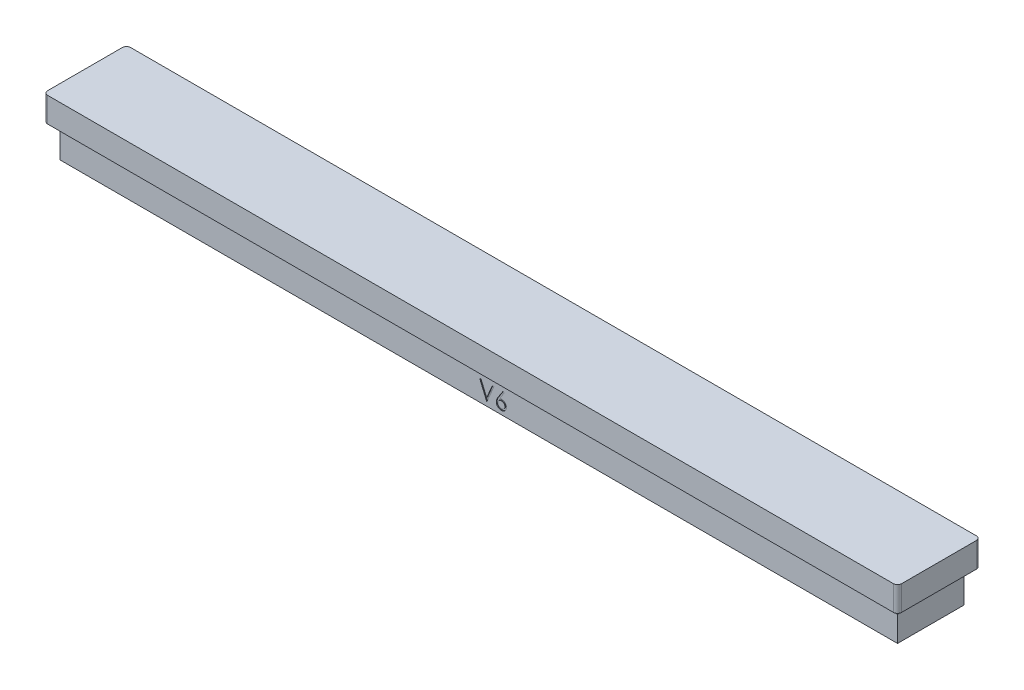
SolidWorks part; units mm, degrees
ref_plane "Front Plane" through (0, 0, 0) normal (0, 0, 1) x (1, 0, 0)
ref_plane "Top Plane" through (0, 0, 0) normal (0, 1, 0) x (1, 0, 0)
ref_plane "Right Plane" through (0, 0, 0) normal (1, 0, 0) x (0, 0, -1)
sketch "Sketch1" plane through (0, 0, 0) normal (0, 1, 0) x (1, 0, 0)
  line L0 (-50.5, 4) -> (-50.5, -4)
  line L1 (-49.5, 3) -> (49.5, 3)
  line L2 (-49.5, 3) -> (-49.5, -3)
  line L3 (-49.5, -3) -> (49.5, -3)
  line L4 (49.5, 3) -> (49.5, -3)
  line L5 (-49.5, 3) -> (49.5, -3) construction
  line L6 (-49.5, -3) -> (49.5, 3) construction
  line L7 (-50.5, -4) -> (50.5, -4)
  line L8 (50.5, 4) -> (50.5, -4)
  line L9 (-50.5, 4) -> (50.5, 4)
  point P0 (0, 0)
  dimension "D1" = 6
  dimension "D2" = 99
  dimension "D3" = 1
extrude "Boss-Extrude1" add sketch "Sketch1" along normal blind 10
sketch "Sketch2" plane through (0, 0, 0) normal (0, -1, 0) x (1, 0, 0)
  line L0 (0, 0) -> (74.3491, 0) construction
  line L1 (48, 0) -> (48, 10.5) construction
  line L2 (50.5, 4) -> (50.5, -4) construction
  line L4 (50.5, 4) -> (67.4224, 4) construction
  line L5 (50.5, -4) -> (69.4178, -4) construction
  line L7 (48, 4) -> (50.5, 4)
  line L9 (48, -4) -> (50.5, -4)
  line L11 (48, 0) -> (48, -8.5) construction
  line L15 (50.5, 4) -> (50.5, 13)
  line L16 (50.5, 13) -> (50, 13) construction
  line L17 (50.5, -4) -> (50.5, -11)
  line L18 (50.5, -11) -> (50, -11) construction
  line L19 (48, 10.5) -> (48, 4)
  line L20 (48, -8.5) -> (48, -4)
  line L21 (-50.5, 4) -> (-50.5, 13) construction
  line L22 (-50.5, 13) -> (-64.4, 13) construction
  line L23 (-66.4, 15) -> (-48.8351, 15)
  line L24 (-48.8351, 15) -> (-48.8351, 4)
  line L25 (-50.5, 4) -> (50.5, 4) construction
  line L26 (-66.4, 11) -> (-51.9017, 11)
  line L27 (-50.5, -4) -> (-59.3527, -4) construction
  line L28 (-51.9017, 11) -> (-51.9017, -4)
  line L29 (-51.9017, -4) -> (-50.5, -4)
  line L30 (-50.5, -4) -> (-50.5, 4)
  line L31 (-50.5, 4) -> (-48.8351, 4)
  line L32 (-64.4, 13) -> (-65.2, 13) construction
  line L33 (-65.2, 13) -> (-66.4, 13) construction
  line L34 (48, 10.5) -> (48, 11) construction
  line L35 (48, 11) -> (48, 13) construction
  line L36 (48, 11) -> (48, 10.5) construction
  line L37 (48, -8.5) -> (48, -9) construction
  line L38 (48, -9) -> (48, -11) construction
  line L39 (48, -9) -> (48, -8.5) construction
  circle A0 centre (48, 13) radius 1.2
  circle A4 centre (48, -11) radius 1.2
  arc A5 (50.5, -11) -> (48, -8.5) centre (48, -11) ccw construction
  arc A8 (48, 10.5) -> (50.5, 13) centre (48, 13) ccw construction
  circle A10 centre (-66.4, 13) radius 1.2
  arc A11 (-66.4, 15) -> (-66.4, 11) centre (-66.4, 13) ccw
  arc A12 (-64.4, 13) -> (-66.4, 15) centre (-66.4, 13) ccw construction
  arc A13 (-66.4, 11) -> (-64.4, 13) centre (-66.4, 13) ccw construction
  arc A14 (50.5, 13) -> (48, 10.5) centre (48, 13) ccw
  arc A15 (48, -8.5) -> (50.5, -11) centre (48, -11) ccw
  dimension "D3" = 2.4
  dimension "D9" = 2.4
  dimension "D10" = 4
  dimension "D1" = 2.5
  dimension "D2" = 13
  dimension "D5" = 11
  dimension "D7" = 9
  dimension "D8" = 15.9
extrude "Boss-Extrude2" [suppressed] add sketch "Sketch2" against normal blind 2
sketch "Sketch3" plane through (0, 10, 0) normal (0, 1, 0) x (1, 0, 0)
  line L0 (51.5, 5) -> (-51.5, 5)
  line L1 (-51.5, 5) -> (-51.5, -5)
  line L2 (-51.5, -5) -> (51.5, -5)
  line L3 (51.5, -5) -> (51.5, 5)
  line L4 (50.5, 4) -> (-50.5, 4)
  line L5 (-50.5, 4) -> (-50.5, -4)
  line L6 (-50.5, -4) -> (50.5, -4)
  line L7 (50.5, -4) -> (50.5, 4)
  line L8 (50.5, 4) -> (-50.5, 4)
  line L9 (-50.5, 4) -> (-50.5, -4)
  line L10 (-50.5, -4) -> (50.5, -4)
  line L11 (50.5, -4) -> (50.5, 4)
  dimension "D1" = 0
  dimension "D2" = 1
extrude "Boss-Extrude3" add sketch "Sketch3" against normal blind 6
fillet "Fillet4" radius 1 1 edges at (0, 4, -4)
fillet "Fillet5" radius 1 1 edges at (0, 4, 4)
fillet "Fillet6" radius 1 1 edges at (50.5, 4, 0)
fillet "Fillet7" radius 1 1 edges at (-50.5, 4, 0)
fillet "Fillet8" [suppressed] radius 0.5
fillet "Fillet9" radius 0.5 4 edges at (51.5, 7, -5) (51.5, 7, 5) (-51.5, 7, 5) (-51.5, 7, -5)
sketch "Sketch4" plane through (0, 10, 0) normal (0, 1, 0) x (1, 0, 0)
  line L4 (51.5, -4.5) -> (51.5, 4.5)
  line L5 (51, 5) -> (-51, 5)
  line L6 (-51.5, 4.5) -> (-51.5, -4.5)
  line L7 (-51, -5) -> (51, -5)
  line L8 (51.5, -4.5) -> (51.5, 4.5)
  line L9 (51, 5) -> (-51, 5)
  line L10 (-51.5, 4.5) -> (-51.5, -4.5)
  line L11 (-51, -5) -> (51, -5)
  arc A4 (51.5, 4.5) -> (51, 5) centre (51, 4.5) ccw
  arc A5 (-51, 5) -> (-51.5, 4.5) centre (-51, 4.5) ccw
  arc A6 (-51.5, -4.5) -> (-51, -5) centre (-51, -4.5) ccw
  arc A7 (51, -5) -> (51.5, -4.5) centre (51, -4.5) ccw
  arc A8 (51.5, 4.5) -> (51, 5) centre (51, 4.5) ccw
  arc A9 (-51, 5) -> (-51.5, 4.5) centre (-51, 4.5) ccw
  arc A10 (-51.5, -4.5) -> (-51, -5) centre (-51, -4.5) ccw
  arc A11 (51, -5) -> (51.5, -4.5) centre (51, -4.5) ccw
  dimension "D1" = 0
extrude "Cut-Extrude1" cut sketch "Sketch4" against normal blind 4
sketch "Sketch5" plane through (0, 0, 4) normal (0, 0, 1) x (1, 0, 0)
  text T0 "V6\r\n\r\n" font "Century Gothic" height 2
extrude "Cut-Extrude2" cut sketch "Sketch5" against normal blind 0.1
sketch "Sketch7" plane through (0, 6, 0) normal (0, 1, 0) x (1, 0, 0)
  line L4 (51.5, -4.5) -> (51.5, 4.5)
  line L5 (51, 5) -> (-51, 5)
  line L6 (-51.5, 4.5) -> (-51.5, -4.5)
  line L7 (-51, -5) -> (51, -5)
  line L8 (51.5, -4.5) -> (51.5, 4.5)
  line L9 (51, 5) -> (-51, 5)
  line L10 (-51.5, 4.5) -> (-51.5, -4.5)
  line L11 (-51, -5) -> (51, -5)
  arc A4 (51, -5) -> (51.5, -4.5) centre (51, -4.5) ccw
  arc A5 (51.5, 4.5) -> (51, 5) centre (51, 4.5) ccw
  arc A6 (-51, 5) -> (-51.5, 4.5) centre (-51, 4.5) ccw
  arc A7 (-51.5, -4.5) -> (-51, -5) centre (-51, -4.5) ccw
  arc A8 (51, -5) -> (51.5, -4.5) centre (51, -4.5) ccw
  arc A9 (51.5, 4.5) -> (51, 5) centre (51, 4.5) ccw
  arc A10 (-51, 5) -> (-51.5, 4.5) centre (-51, 4.5) ccw
  arc A11 (-51.5, -4.5) -> (-51, -5) centre (-51, -4.5) ccw
  dimension "D1" = 0
extrude "Boss-Extrude4" add sketch "Sketch7" along normal blind 1
sketch "Sketch8" [suppressed] plane through (0, 2, 0) normal (0, 1, 0) x (1, 0, 0)
  line L0 (50.5, 4) -> (50.5, 11) construction
  line L1 (48, 8.5) -> (48, 4) construction
  line L2 (48, 4) -> (50.5, 4) construction
  line L3 (50.5, -13) -> (50.5, -4) construction
  line L4 (50.5, -4) -> (48, -4) construction
  line L5 (48, -4) -> (48, -10.5) construction
  line L6 (-66.4, -15) -> (-49.3351, -15) construction
  line L7 (-48.8351, -14.5) -> (-48.8351, -4) construction
  line L8 (-48.8351, -4) -> (-50.5, -4) construction
  line L9 (-50.5, -4) -> (-50.5, 4) construction
  line L10 (-50.5, 4) -> (-51.9017, 4) construction
  line L11 (-51.9017, 4) -> (-51.9017, -10.5) construction
  line L12 (-52.4017, -11) -> (-66.4, -11) construction
  line L13 (50.5, 4) -> (50.5, 11)
  line L14 (48, 8.5) -> (48, 4)
  line L15 (48, 4) -> (50.5, 4)
  line L16 (50.5, -13) -> (50.5, -4)
  line L17 (50.5, -4) -> (48, -4)
  line L18 (48, -4) -> (48, -10.5)
  line L19 (-66.4, -15) -> (-49.3351, -15)
  line L20 (-48.8351, -14.5) -> (-48.8351, -4)
  line L21 (-48.8351, -4) -> (-50.5, -4)
  line L22 (-50.5, -4) -> (-50.5, 4)
  line L23 (-50.5, 4) -> (-51.9017, 4)
  line L24 (-51.9017, 4) -> (-51.9017, -10.5)
  line L25 (-52.4017, -11) -> (-66.4, -11)
  arc A0 (50.5, 11) -> (48, 8.5) centre (48, 11) ccw construction
  arc A1 (48, -10.5) -> (50.5, -13) centre (48, -13) ccw construction
  arc A2 (-49.3351, -15) -> (-48.8351, -14.5) centre (-49.3351, -14.5) ccw construction
  arc A3 (-52.4017, -11) -> (-51.9017, -10.5) centre (-52.4017, -10.5) ccw construction
  arc A4 (-66.4, -11) -> (-66.4, -15) centre (-66.4, -13) ccw construction
  arc A5 (50.5, 11) -> (48, 8.5) centre (48, 11) ccw
  arc A6 (48, -10.5) -> (50.5, -13) centre (48, -13) ccw
  arc A7 (-49.3351, -15) -> (-48.8351, -14.5) centre (-49.3351, -14.5) ccw
  arc A8 (-52.4017, -11) -> (-51.9017, -10.5) centre (-52.4017, -10.5) ccw
  arc A9 (-66.4, -11) -> (-66.4, -15) centre (-66.4, -13) ccw
  circle A10 centre (48, 11) radius 1.2 construction
  circle A11 centre (48, -13) radius 1.2 construction
  circle A12 centre (-66.4, -13) radius 1.2 construction
  circle A13 centre (48, 11) radius 1.2
  circle A14 centre (48, -13) radius 1.2
  circle A15 centre (-66.4, -13) radius 1.2
extrude "Boss-Extrude5" [suppressed] add sketch "Sketch8" along normal blind 2
fillet "Fillet10" [suppressed] radius 1
sketch "Sketch9" plane through (0, 6, 0) normal (0, -1, 0) x (1, 0, 0)
  line L0 (0, 0) -> (-60.7592, 0) construction
  line L1 (-49.5, -3) -> (-49.5, 3) construction
  line L2 (-46.5, 2.5) -> (-43.5, 2.5)
  line L3 (-46.5, 2.5) -> (-46.5, -2.5)
  line L4 (-46.5, -2.5) -> (-43.5, -2.5)
  line L5 (-43.5, 2.5) -> (-43.5, -2.5)
  line L6 (-46.5, 2.5) -> (-43.5, -2.5) construction
  line L7 (-46.5, -2.5) -> (-43.5, 2.5) construction
  line L8 (-37.5, 2.5) -> (-37.5, -2.5)
  line L9 (-40.5, 2.5) -> (-40.5, -2.5)
  line L10 (-40.5, 2.5) -> (-37.5, 2.5)
  line L11 (-40.5, -2.5) -> (-37.5, -2.5)
  line L12 (-31.5, 2.5) -> (-31.5, -2.5)
  line L13 (-34.5, 2.5) -> (-34.5, -2.5)
  line L14 (-34.5, 2.5) -> (-31.5, 2.5)
  line L15 (-34.5, -2.5) -> (-31.5, -2.5)
  line L16 (-25.5, 2.5) -> (-25.5, -2.5)
  line L17 (-28.5, 2.5) -> (-28.5, -2.5)
  line L18 (-28.5, 2.5) -> (-25.5, 2.5)
  line L19 (-28.5, -2.5) -> (-25.5, -2.5)
  line L20 (-19.5, 2.5) -> (-19.5, -2.5)
  line L21 (-22.5, 2.5) -> (-22.5, -2.5)
  line L22 (-22.5, 2.5) -> (-19.5, 2.5)
  line L23 (-22.5, -2.5) -> (-19.5, -2.5)
  line L24 (-13.5, 2.5) -> (-13.5, -2.5)
  line L25 (-16.5, 2.5) -> (-16.5, -2.5)
  line L26 (-16.5, 2.5) -> (-13.5, 2.5)
  line L27 (-16.5, -2.5) -> (-13.5, -2.5)
  line L28 (-7.5, 2.5) -> (-7.5, -2.5)
  line L29 (-10.5, 2.5) -> (-10.5, -2.5)
  line L30 (-10.5, 2.5) -> (-7.5, 2.5)
  line L31 (-10.5, -2.5) -> (-7.5, -2.5)
  line L32 (-1.5, 2.5) -> (-1.5, -2.5)
  line L33 (-4.5, 2.5) -> (-4.5, -2.5)
  line L34 (-4.5, 2.5) -> (-1.5, 2.5)
  line L35 (-4.5, -2.5) -> (-1.5, -2.5)
  line L36 (4.5, 2.5) -> (4.5, -2.5)
  line L37 (1.5, 2.5) -> (1.5, -2.5)
  line L38 (1.5, 2.5) -> (4.5, 2.5)
  line L39 (1.5, -2.5) -> (4.5, -2.5)
  line L40 (10.5, 2.5) -> (10.5, -2.5)
  line L41 (7.5, 2.5) -> (7.5, -2.5)
  line L42 (7.5, 2.5) -> (10.5, 2.5)
  line L43 (7.5, -2.5) -> (10.5, -2.5)
  line L44 (16.5, 2.5) -> (16.5, -2.5)
  line L45 (13.5, 2.5) -> (13.5, -2.5)
  line L46 (13.5, 2.5) -> (16.5, 2.5)
  line L47 (13.5, -2.5) -> (16.5, -2.5)
  line L48 (22.5, 2.5) -> (22.5, -2.5)
  line L49 (19.5, 2.5) -> (19.5, -2.5)
  line L50 (19.5, 2.5) -> (22.5, 2.5)
  line L51 (19.5, -2.5) -> (22.5, -2.5)
  line L52 (28.5, 2.5) -> (28.5, -2.5)
  line L53 (25.5, 2.5) -> (25.5, -2.5)
  line L54 (25.5, 2.5) -> (28.5, 2.5)
  line L55 (25.5, -2.5) -> (28.5, -2.5)
  line L56 (34.5, 2.5) -> (34.5, -2.5)
  line L57 (31.5, 2.5) -> (31.5, -2.5)
  line L58 (31.5, 2.5) -> (34.5, 2.5)
  line L59 (31.5, -2.5) -> (34.5, -2.5)
  line L60 (40.5, 2.5) -> (40.5, -2.5)
  line L61 (37.5, 2.5) -> (37.5, -2.5)
  line L62 (37.5, 2.5) -> (40.5, 2.5)
  line L63 (37.5, -2.5) -> (40.5, -2.5)
  line L64 (46.5, 2.5) -> (46.5, -2.5)
  line L65 (43.5, 2.5) -> (43.5, -2.5)
  line L66 (43.5, 2.5) -> (46.5, 2.5)
  line L67 (43.5, -2.5) -> (46.5, -2.5)
  point P3 (-45, 0)
  dimension "D1" = 3
  dimension "D2" = 5
  dimension "D3" = 3
  dimension "D4" = 16
extrude "Boss-Extrude6" add sketch "Sketch9" along normal blind 1.2
